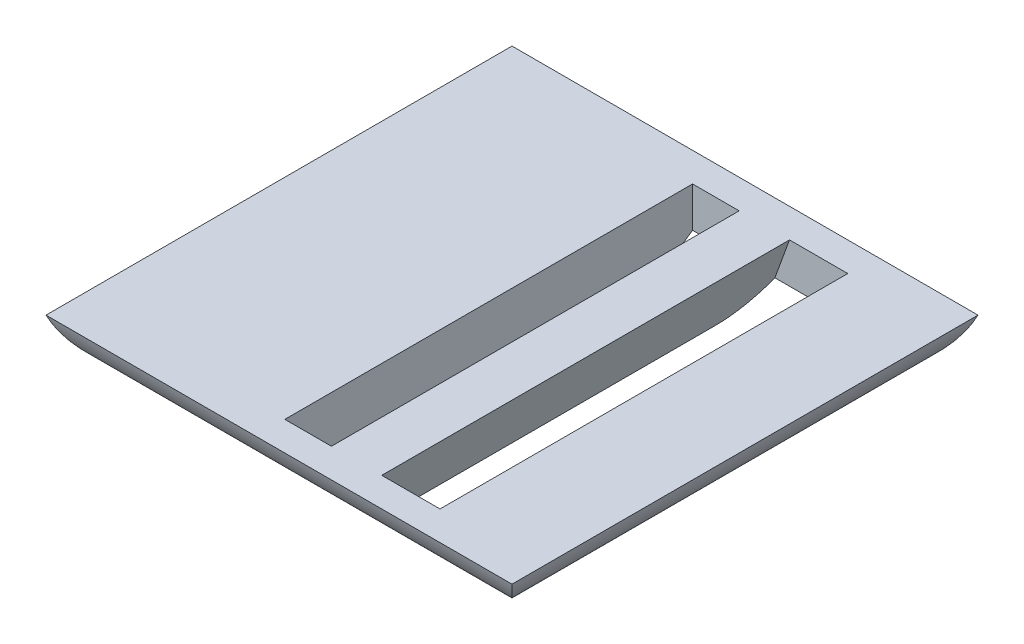
SolidWorks part; units mm, degrees
ref_plane "Front Plane" through (0, 0, 0) normal (0, 0, 1) x (1, 0, 0)
ref_plane "Top Plane" through (0, 0, 0) normal (0, 1, 0) x (1, 0, 0)
ref_plane "Right Plane" through (0, 0, 0) normal (1, 0, 0) x (0, 0, -1)
sketch "Sketch1" plane through (0, 0, 0) normal (0, 1, 0) x (1, 0, 0)
  line L1 (40, -40) -> (-40, -40)
  line L2 (40, -40) -> (40, 40)
  line L3 (40, 40) -> (-40, 40)
  line L4 (-40, -40) -> (-40, 40)
  line L5 (40, -40) -> (-40, 40) construction
  line L6 (40, 40) -> (-40, -40) construction
  point P0 (0, 0)
  dimension "D1" = 80
  dimension "D2" = 80
extrude "Boss-Extrude1" add sketch "Sketch1" along normal blind 10
sketch "Sketch2" plane through (0, 0, 0) normal (0, -1, 0) x (1, 0, 0)
  line L1 (4, -35) -> (-4, -35)
  line L2 (4, -35) -> (4, 35)
  line L3 (4, 35) -> (-4, 35)
  line L4 (-4, -35) -> (-4, 35)
  line L5 (4, -35) -> (-4, 35) construction
  line L6 (4, 35) -> (-4, -35) construction
  point P0 (0, 0)
  dimension "D1" = 70
  dimension "D2" = 8
extrude "Cut-Extrude1" cut sketch "Sketch2" against normal blind 20
sketch "Sketch8" plane through (0, 0, -40) normal (0, 0, -1) x (-1, 0, 0)
  line L0 (-19, 0) -> (-22.6397, 10)
  line L1 (-40, 0) -> (40, 0) construction
  line L2 (-40, 10) -> (40, 10) construction
  line L3 (-9, 0) -> (-12.6397, 10)
  line L4 (-12.6397, 10) -> (-22.6397, 10)
  line L5 (-9, 0) -> (-19, 0)
  dimension "D1" = 15
  dimension "D2" = 70
  dimension "D3" = 10
  dimension "D4" = 10
extrude "Cut-Extrude17" cut sketch "Sketch8" against normal blind 75
sketch "Sketch10" plane through (0, 0, -40) normal (0, 0, -1) x (-1, 0, 0)
  line L0 (-9, 0) -> (-12.6397, 10)
  line L1 (-12.6397, 10) -> (-22.6397, 10)
  line L2 (-22.6397, 10) -> (-19, 0)
  line L3 (-19, 0) -> (-9, 0)
extrude "Boss-Extrude2" add sketch "Sketch10" against normal blind 5
fillet "Fillet1" radius 15 4 edges at (-40, 0, 0) (0, 0, -40) (40, 0, 0) (0, 0, 40)
